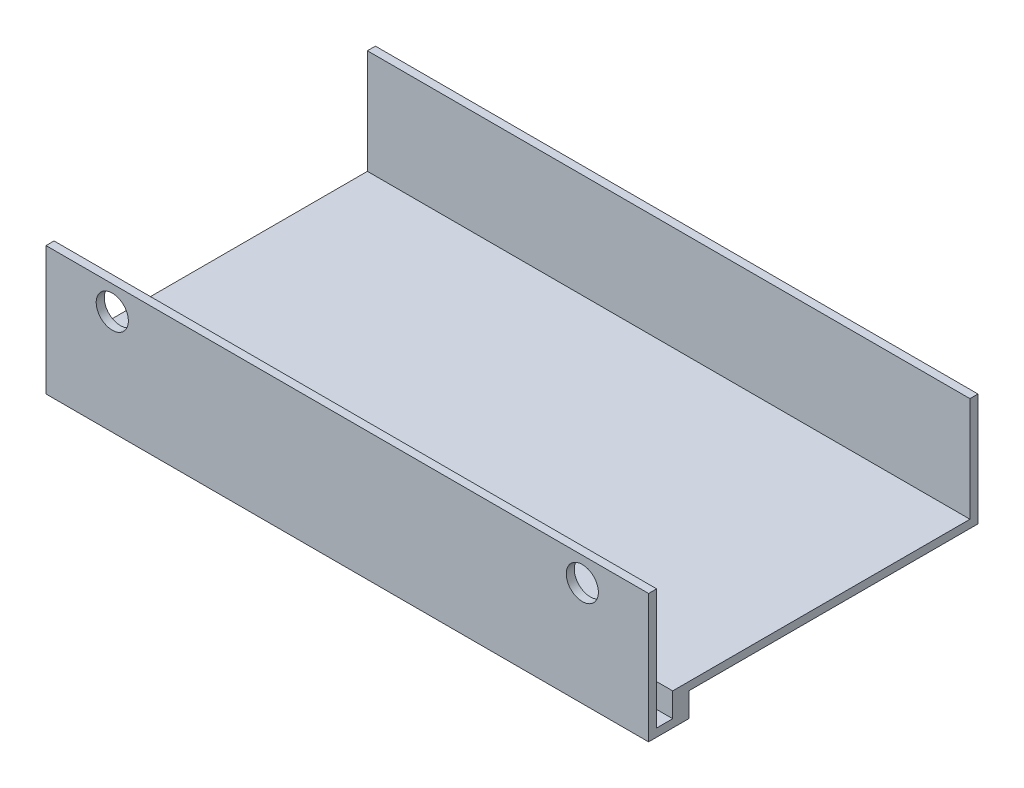
SolidWorks part; units mm, degrees
ref_plane "Plan de face" through (0, 0, 0) normal (0, 0, 1) x (1, 0, 0)
ref_plane "Plan de dessus" through (0, 0, 0) normal (0, 1, 0) x (1, 0, 0)
ref_plane "Plan de droite" through (0, 0, 0) normal (1, 0, 0) x (0, 0, -1)
sketch "Esquisse1" plane through (0, 0, 0) normal (0, 0, 1) x (1, 0, 0)
  line L1 (0, 0) -> (75, 0)
  line L2 (0, 0) -> (0, 15)
  line L3 (0, 15) -> (75, 15)
  line L4 (75, 0) -> (75, 15)
  line L5 (0, 0) -> (75, 0)
  line L6 (0, 0) -> (0, -1)
  line L7 (0, -1) -> (75, -1)
  line L8 (75, 0) -> (75, -1)
  circle A0 centre (8.25, 12) radius 2
  circle A1 centre (66.75, 12) radius 2
  dimension "D6" = 4
  dimension "D7" = 4
  dimension "D1" = 15
  dimension "D2" = 75
  dimension "D3" = 8.25
  dimension "D4" = 8.25
  dimension "D5" = 12
  dimension "D8" = 12
  dimension "D9" = 75
  dimension "D10" = 1
extrude "Boss.-Extru.1" add sketch "Esquisse1" along normal blind 1 contours L1 L4 L3 L2 A1 A0 | L8 L1 L6 L7 region at (37.5, 7.3972, 0) region at (37.5, -0.5, 0)
extrude "Boss.-Extru.2" add sketch "Esquisse1<3>" against normal blind 40 contours L8 L1 L6 L7 region at (37.5, -0.5, 0)
sketch "Esquisse1<3>" plane through (0, 0, 0) normal (0, 0, 1) x (1, 0, 0) same geometry as "Esquisse1"
sketch "Esquisse2" plane through (0, 0, 0) normal (0, 1, 0) x (1, 0, 0)
  line L0 (0, 40) -> (0, 0) construction
  line L1 (75, 40) -> (0, 40)
  line L2 (75, 40) -> (75, 39)
  line L3 (75, 39) -> (0, 39)
  line L4 (0, 40) -> (0, 39)
  dimension "D1" = 1
extrude "Boss.-Extru.3" add sketch "Esquisse2" along normal blind 16
sketch "Esquisse3" plane through (0, -1, 0) normal (0, -1, 0) x (1, 0, 0)
  line L0 (0, 1) -> (75, 1) construction
  line L1 (5, -4) -> (70, -4)
  line L2 (5, -4) -> (5, -37)
  line L3 (5, -37) -> (70, -37)
  line L4 (70, -4) -> (70, -37)
  line L5 (0, -40) -> (75, -40) construction
  line L6 (0, 1) -> (0, -40) construction
  line L7 (75, 1) -> (75, -40) construction
  dimension "D1" = 5
  dimension "D2" = 3
  dimension "D3" = 5
  dimension "D4" = 5
extrude "Enlèv. mat.-Extru.1" cut sketch "Esquisse3" against normal blind 3
sketch "Esquisse4" plane through (0, 0, 0) normal (0, 1, 0) x (1, 0, 0)
  line L0 (75, 39) -> (75, 0) construction
  line L1 (75, 2) -> (0, 2)
  line L2 (75, 2) -> (75, 39)
  line L3 (75, 39) -> (0, 39)
  line L4 (0, 2) -> (0, 39)
  line L5 (0, 39) -> (75, 39) construction
  line L6 (0, 39) -> (0, 0) construction
  dimension "D1" = 37
extrude "Boss.-Extru.4" add sketch "Esquisse4" along normal blind 3
sketch "Esquisse5" plane through (0, -1, 0) normal (0, -1, 0) x (1, 0, 0)
  line L0 (0, 1) -> (0, -40) construction
  line L1 (0, -4) -> (75, -4)
  line L2 (0, -4) -> (0, -40)
  line L3 (0, -40) -> (75, -40)
  line L4 (75, -4) -> (75, -40)
  dimension "D1" = 36
extrude "Enlèv. mat.-Extru.2" cut sketch "Esquisse5" against normal blind 3
